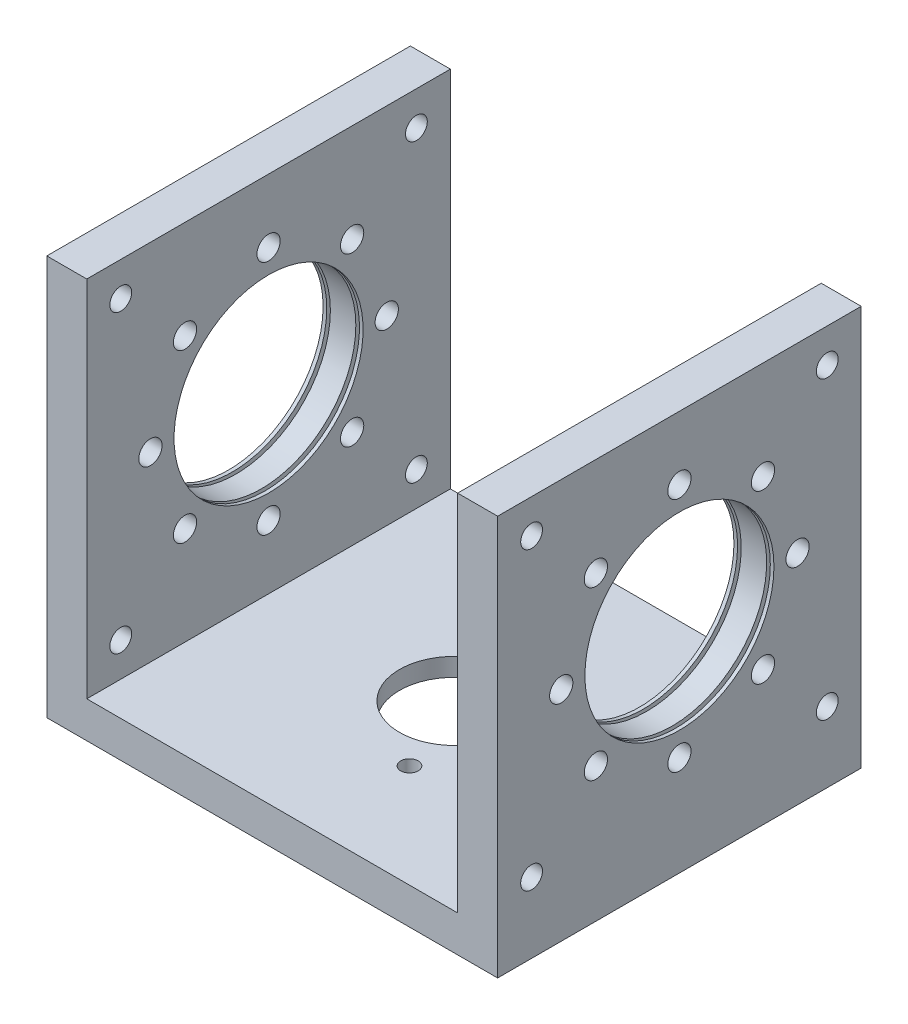
SolidWorks part; units mm, degrees
ref_plane "Front Plane" through (0, 0, 0) normal (0, 0, 1) x (1, 0, 0)
ref_plane "Top Plane" through (0, 0, 0) normal (0, 1, 0) x (1, 0, 0)
ref_plane "Right Plane" through (0, 0, 0) normal (1, 0, 0) x (0, 0, -1)
sketch "Sketch1" plane through (0, 0, 0) normal (0, 0, 1) x (1, 0, 0)
  line L0 (0, 0) -> (0, 110)
  line L1 (0, 110) -> (11, 110)
  line L2 (11, 110) -> (11, 10)
  line L3 (11, 10) -> (113, 10)
  line L4 (113, 10) -> (113, 110)
  line L5 (113, 110) -> (124, 110)
  line L6 (124, 110) -> (124, 0)
  line L7 (124, 0) -> (0, 0)
  dimension "D1" = 102
  dimension "D2" = 11
  dimension "D3" = 110
  dimension "D4" = 10
extrude "Boss-Extrude1" add sketch "Sketch1" along normal blind 100
sketch "Sketch2" plane through (0, 10, 0) normal (0, 1, 0) x (1, 0, 0)
  line L0 (11, 0) -> (113, 0)
  line L1 (11, 0) -> (11, -100)
  circle A0 centre (62, -50) radius 41
  dimension "D3" = 82
  dimension "D1" = 102
  dimension "D2" = 100
  dimension "D4" = 50
  dimension "D5" = 51
extrude "Cut-Extrude1" cut sketch "Sketch2" against normal through all from offset 5 contours A0 region at (62, 10, 50) offset against normal yes
sketch "Sketch3" plane through (0, 5, 0) normal (0, -1, 0) x (1, 0, 0)
  circle A0 centre (62, 50) radius 15
  dimension "D1" = 30
extrude "Cut-Extrude2" cut sketch "Sketch3" against normal blind 10
sketch "Sketch4" plane through (11, 0, 0) normal (1, 0, 0) x (0, 0, -1)
  line L0 (-90.6586, 100.6586) -> (-100, 100.6586) construction
  line L1 (-100, 10) -> (-100, 110) construction
  line L2 (-90.6586, 100.6586) -> (-90.6586, 110) construction
  line L3 (-100, 110) -> (0, 110) construction
  line L4 (-9.3414, 100.6586) -> (-9.3414, 110) construction
  line L5 (-9.3414, 100.6586) -> (0, 100.6586) construction
  line L6 (0, 10) -> (0, 110) construction
  line L7 (-9.3414, 19.3414) -> (0, 19.3414) construction
  line L8 (-9.3414, 19.3414) -> (-9.3414, 10) construction
  line L9 (-100, 10) -> (0, 10) construction
  line L10 (-90.6586, 19.3414) -> (-90.6586, 10.0664) construction
  line L11 (-90.6586, 19.3414) -> (-100, 19.3414) construction
  circle A0 centre (-50, 60) radius 57.5 construction
  circle A1 centre (-50, 117.5) radius 3
  circle A2 centre (-9.3414, 100.6586) radius 3
  circle A3 centre (7.5, 60) radius 3
  circle A4 centre (-9.3414, 19.3414) radius 3
  circle A5 centre (-50, 2.5) radius 3
  circle A6 centre (-90.6586, 19.3414) radius 3
  circle A7 centre (-107.5, 60) radius 3
  circle A8 centre (-90.6586, 100.6586) radius 3
  point P21 (-50, 60)
  dimension "D1" = 115
  dimension "D2" = 6
  dimension "D3" = 8
extrude "Cut-Extrude3" cut sketch "Sketch4" against normal through all and the other way through all contours A4 | A6 | A8 | A2 region at (11, 100.6586, 9.3414) region at (11, 19.3414, 9.3414) region at (11, 19.3414, 90.6586) region at (11, 100.6586, 90.6586)
hole_wizard "M4 Clearance Hole2" positions "Sketch8" profile "Sketch9" hole size "M4" standard "DIN"
sketch "Sketch8" plane through (0, 10, 0) normal (0, 1, 0) x (1, 0, 0)
  circle A0 centre (62, -50) radius 15 construction
  point P0 (69.404, -30.3485)
  point P10 (91, -50)
  point P11 (71.3485, -71.596)
  point P12 (49.7525, -51.9445)
  dimension "D1" = 21
  dimension "D2" = 4
sketch "Sketch9" plane through (69.404, 10, 30.3485) normal (1, 0, 0) x (0, 0, 1)
  line L0 (0, 0) -> (0, 6.4421)
  line L1 (0, 6.4421) -> (2.4, 5)
  line L2 (2.4, 5) -> (2.4, 0)
  line L5 (2.4, 0) -> (0, 0)
  line L10 (0, 6.4421) -> (-2.4, 5) construction
  line L11 (0, -6.35) -> (0, 107.95) construction
  dimension "Hole Dia." = 4.8
  dimension "Hole Depth" = 5
  dimension "Drill Angle" = 118
sketch "Sketch10" plane through (124, 0, 0) normal (1, 0, 0) x (0, 0, -1)
  line L0 (-90.6586, 100.6586) -> (-9.3414, 19.3414) construction
  line L1 (-9.3414, 100.6586) -> (-90.6586, 19.3414) construction
  circle A0 centre (-50, 60) radius 26
  dimension "D1" = 52
extrude "Cut-Extrude5" cut sketch "Sketch10" against normal blind 193
hole_wizard "M6 Clearance Hole1" positions "Sketch12" profile "Sketch13" hole size "M6" standard "DIN" end condition through all
sketch "Sketch12" plane through (124, 0, 0) normal (1, 0, 0) x (0, 0, -1)
  circle A0 centre (-50, 60) radius 32.5 construction
  point P11 (-50, 92.5)
  point P19 (-27.019, 82.981)
  point P20 (-17.5, 60)
  point P21 (-27.019, 37.019)
  point P22 (-50, 27.5)
  point P23 (-72.981, 37.019)
  point P24 (-82.5, 60)
  point P25 (-72.981, 82.981)
  dimension "D1" = 65
  dimension "D2" = 8
sketch "Sketch13" plane through (124, 82.981, 72.981) normal (0, 1, 0) x (0, 0, -1)
  line L0 (0, 0) -> (0, 124)
  line L1 (0, 124) -> (3.2, 124)
  line L2 (3.2, 124) -> (3.2, 0)
  line L5 (3.2, 0) -> (0, 0)
  line L11 (0, -6.35) -> (0, 107.95) construction
  dimension "Thru Hole Dia." = 6.4
  dimension "Thru Hole Depth" = 124
sketch "Sketch14" plane through (124, 0, 0) normal (1, 0, 0) x (0, 0, -1)
  circle A0 centre (-50, 60) radius 27.6
  dimension "D1" = 55.2
extrude "Cut-Extrude6" cut sketch "Sketch14" against normal blind 1 from offset 1 offset against normal yes
extrude "Cut-Extrude7" cut sketch "Sketch14<2>" along normal blind 1 from offset 10 offset against normal yes
sketch "Sketch14<2>" plane through (124, 0, 0) normal (1, 0, 0) x (0, 0, -1) same geometry as "Sketch14"
sketch "Sketch15" plane through (0, 0, 0) normal (-1, 0, 0) x (0, 0, 1)
  circle A0 centre (50, 60) radius 27.6
  dimension "D1" = 55.2
extrude "Cut-Extrude8" cut sketch "Sketch15" against normal blind 1 from offset 1 offset against normal yes
extrude "Cut-Extrude9" cut sketch "Sketch15<2>" along normal blind 1 from offset 10 offset against normal yes
sketch "Sketch15<2>" plane through (0, 0, 0) normal (-1, 0, 0) x (0, 0, 1) same geometry as "Sketch15"
equation "\"D5@Sketch2\"=\"D1@Sketch2\"/2"
equation "\"D4@Sketch2\"=\"D2@Sketch2\"/2"
